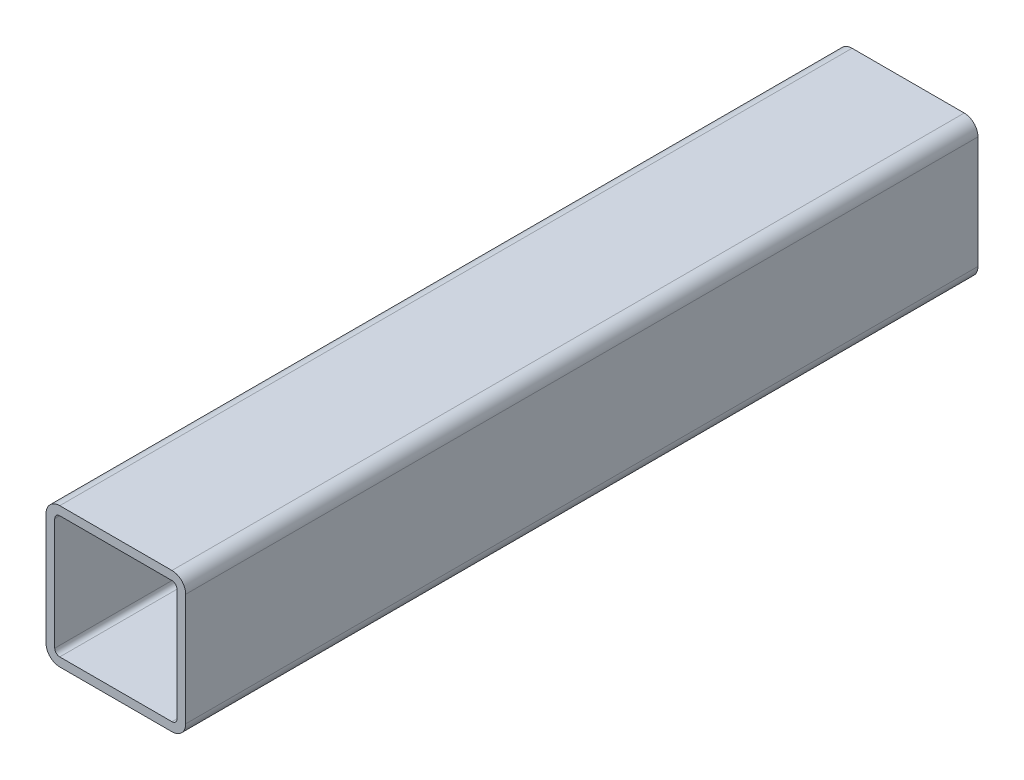
SolidWorks part; units mm, degrees
ref_plane "Front Plane" through (0, 0, 0) normal (0, 0, 1) x (1, 0, 0)
ref_plane "Top Plane" through (0, 0, 0) normal (0, 1, 0) x (1, 0, 0)
ref_plane "Right Plane" through (0, 0, 0) normal (1, 0, 0) x (0, 0, -1)
sketch "Sketch1" plane through (0, 0, 0) normal (0, 0, 1) x (1, 0, 0)
  line L7 (-20.4, 25.4) -> (20.4, 25.4)
  line L8 (25.4, 20.4) -> (25.4, -20.4)
  line L9 (-22.225, 20.4) -> (-22.225, -20.4)
  line L10 (-20.4, -22.225) -> (20.4, -22.225)
  line L11 (20.4, -25.4) -> (-20.4, -25.4)
  line L12 (-25.4, -20.4) -> (-25.4, 20.4)
  line L13 (0, 25.4) -> (0, -25.4) construction
  line L14 (-25.4, 0) -> (25.4, 0) construction
  line L15 (22.225, -20.4) -> (22.225, 20.4)
  line L16 (20.4, 22.225) -> (-20.4, 22.225)
  line L17 (0, 22.225) -> (0, -22.225) construction
  line L18 (-22.225, 0) -> (22.225, 0) construction
  arc A0 (20.4, 25.4) -> (25.4, 20.4) centre (20.4, 20.4) cw
  arc A1 (25.4, -20.4) -> (20.4, -25.4) centre (20.4, -20.4) cw
  arc A2 (-20.4, -25.4) -> (-25.4, -20.4) centre (-20.4, -20.4) cw
  arc A3 (-25.4, 20.4) -> (-20.4, 25.4) centre (-20.4, 20.4) cw
  arc A4 (-22.225, -20.4) -> (-20.4, -22.225) centre (-20.4, -20.4) ccw
  arc A5 (20.4, -22.225) -> (22.225, -20.4) centre (20.4, -20.4) ccw
  arc A6 (22.225, 20.4) -> (20.4, 22.225) centre (20.4, 20.4) ccw
  arc A7 (-20.4, 22.225) -> (-22.225, 20.4) centre (-20.4, 20.4) ccw
  point P39 (0, 0)
  dimension "D1" = 5
  dimension "D2" = 50.8
  dimension "D3" = 3.175
extrude "Boss-Extrude1" add sketch "Sketch1" along normal blind 288.1
